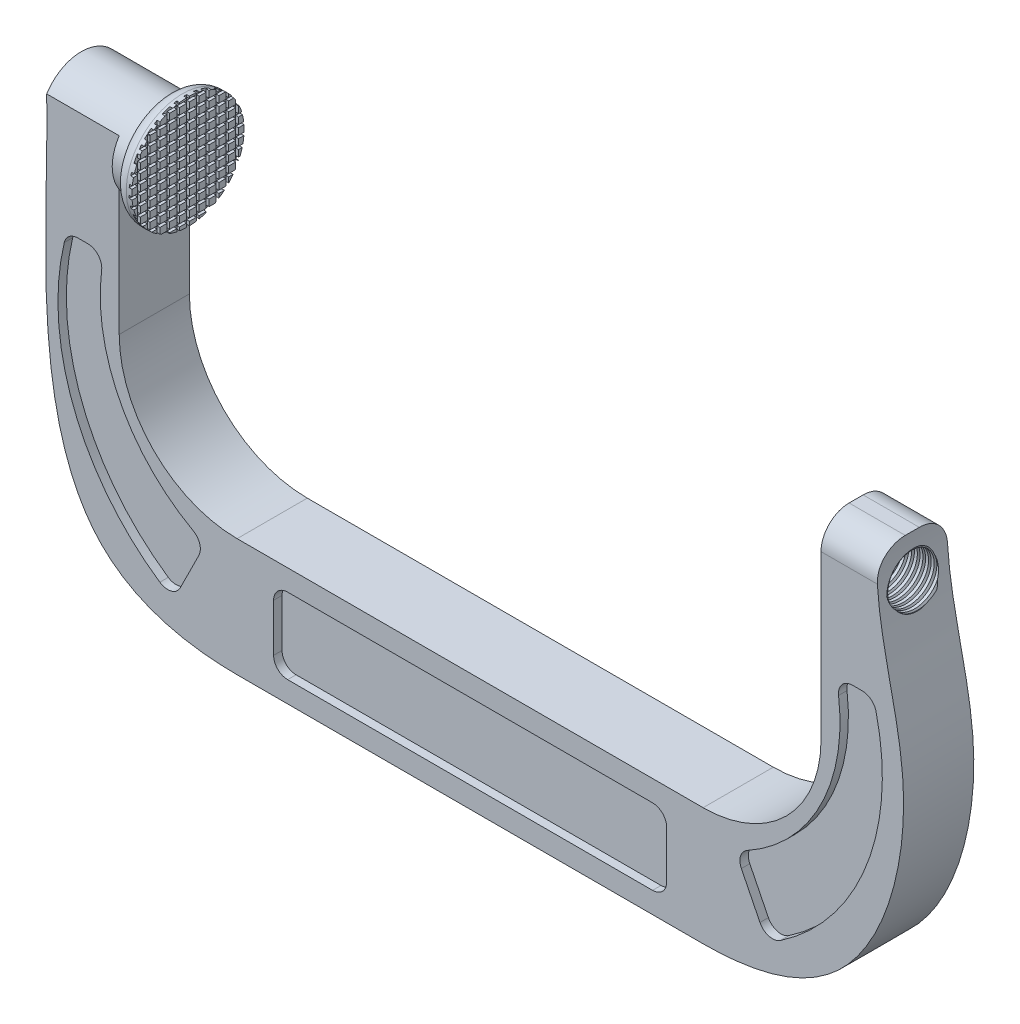
SolidWorks part; units mm, degrees
ref_plane "Front Plane" through (0, 0, 0) normal (0, 0, 1) x (1, 0, 0)
ref_plane "Top Plane" through (0, 0, 0) normal (0, 1, 0) x (1, 0, 0)
ref_plane "Right Plane" through (0, 0, 0) normal (1, 0, 0) x (0, 0, -1)
sketch "Sketch1" plane through (0, 0, 0) normal (0, 0, 1) x (1, 0, 0)
  line L0 (-263.6404, 0) -> (263.6404, 0) construction
  line L1 (125, 0) -> (125, -68)
  line L2 (83, -110) -> (-83, -110)
  line L3 (-125, -68) -> (-125, 0)
  line L4 (83, -152) -> (-83, -152)
  line L5 (0, 0) -> (0, -239.3038) construction
  line L6 (-151, 0) -> (-151, -68)
  line L7 (-151, 0) -> (-125, 0)
  line L8 (125, 0) -> (145, 0)
  arc A0 (125, -68) -> (83, -110) centre (83, -68) cw
  arc A1 (-83, -110) -> (-125, -68) centre (-83, -68) cw
  arc A4 (-83, -152) -> (-167, -68) centre (-83, -68) cw construction
  arc A5 (167, -68) -> (83, -152) centre (83, -68) cw construction
  spline S0 degree 3 poles (145, 0) (143.8087, -23.9152) (162.6478, -65.6261) (142.699, -139.1924) (104.3754, -151.9598) (83, -152) knots 0 0 0 0 0.358889 0.726266 1 1 1 1
  spline S1 degree 3 poles (-151, 0) (-150.1809, -23.6191) (-153.4891, -65.5445) (-144.2173, -139.5495) (-104.5553, -151.9594) (-83, -152) knots 0 0 0 0 0.358512 0.723962 1 1 1 1
  point P4 (0, 0)
  dimension "D4" = 42
  dimension "D1" = 250
  dimension "D2" = 125
  dimension "D3" = 110
  dimension "D5" = 42
  dimension "D6" = 20
  dimension "D7" = 26
  dimension "D8" = 132.4464
  dimension "D9" = 149.4354
  dimension "D10" = 154.2894
  dimension "D11" = 132.4464
  dimension "D12" = 37.3596
  dimension "D13" = 134.7867
extrude "Boss-Extrude1" add sketch "Sketch1" along normal mid plane 25 contours L7 S1 L6 L4 S0 L8 L1 A0 L2 A1 L3
sketch "Sketch2" plane through (-125, 0, 0) normal (1, 0, 0) x (0, 0, -1)
  line L0 (-12.5, 0) -> (12.5, 0) construction
  line L1 (-12.5, -68) -> (-12.5, 0) construction
  circle A0 centre (0, -15) radius 15
  dimension "D1" = 12.5
  dimension "D2" = 30
extrude "Boss-Extrude2" add sketch "Sketch2" along normal blind 5
sketch "Sketch3" plane through (-125, 0, 0) normal (1, 0, 0) x (0, 0, -1)
  line L2 (0, 0) -> (-12.5, 0)
  line L3 (-12.5, 0) -> (-12.5, -6.7084)
  line L4 (0, 0) -> (-12.5, 0)
  line L5 (-12.5, 0) -> (-12.5, -6.7084)
  line L6 (12.5, -6.7084) -> (12.5, 0)
  line L7 (12.5, 0) -> (0, 0)
  line L8 (12.5, -6.7084) -> (12.5, 0)
  line L9 (12.5, 0) -> (0, 0)
  arc A1 (0, 0) -> (-12.5, -6.7084) centre (0, -15) ccw
  arc A2 (0, 0) -> (-12.5, -6.7084) centre (0, -15) ccw
  arc A3 (12.5, -6.7084) -> (0, 0) centre (0, -15) ccw
  arc A4 (12.5, -6.7084) -> (0, 0) centre (0, -15) ccw
  dimension "D1" = 0
  dimension "D2" = 0
extrude "Cut-Extrude1" cut sketch "Sketch3" against normal through all contours A4 L8 L9
sketch "Sketch4" plane through (-120, 0, 0) normal (1, 0, 0) x (0, 0, -1)
  circle A0 centre (0, -15) radius 20
  circle A2 centre (0, -15) radius 15 construction
  dimension "D1" = 40
extrude "Boss-Extrude3" add sketch "Sketch4" along normal blind 7
fillet "Fillet1" radius 5 1 edges at (-120, -15, -20)
sketch "Sketch5" plane through (125, 0, 0) normal (-1, 0, 0) x (0, 0, 1)
  circle A1 centre (0, -15) radius 8.78
  dimension "D1" = 17.56
extrude "Cut-Extrude2" cut sketch "Sketch5" against normal through all
sketch "Sketch6" plane through (125, 0, 0) normal (-1, 0, 0) x (0, 0, 1)
  circle A0 centre (0, -15) radius 8.78 construction
  circle A1 centre (0, -15) radius 8.78
curve "Helix/Spiral1" pitch 2 height 30 radius 8.78 centre (125, -15, 0) axis (1, 0, 0) start towards (0, 1, 0)
sketch "Sketch7" plane through (0, 0, 0) normal (0, 0, 1) x (1, 0, 0)
  line L7 (125.7044, -6.6267) -> (125, -5.4067)
  line L8 (125, -5.4067) -> (124.2956, -6.6267)
  line L9 (124.2956, -6.6267) -> (125.7044, -6.6267)
  circle A0 centre (125, -6.22) radius 0.4067 construction
  dimension "D1" = 1.22
sweep "Cut-Sweep1" cut profiles "Sketch7" path "Helix/Spiral1" align with end faces yes
fillet "Fillet2" radius 10 2 edges at (135, 0, -12.5) (135, 0, 12.5)
sketch "Sketch8" plane through (0, 0, 12.5) normal (0, 0, 1) x (1, 0, 0)
  line L0 (0, 0) -> (0, -273.0897) construction
  line L1 (83, -110) -> (-83, -110) construction
  line L2 (-70, -117.5) -> (70, -117.5)
  line L3 (-70, -117.5) -> (-70, -144.5)
  line L4 (-70, -144.5) -> (70, -144.5)
  line L5 (70, -117.5) -> (70, -144.5)
  line L6 (-70, -117.5) -> (70, -144.5) construction
  line L7 (-70, -144.5) -> (70, -117.5) construction
  line L8 (130.2763, -45.612) -> (143.5579, -45.612)
  line L9 (94.4159, -117.5) -> (105.7053, -140.2435)
  line L10 (-94.4159, -117.5) -> (-105.7053, -140.2435)
  line L11 (-130.2763, -45.612) -> (-143.5579, -45.612)
  arc A0 (130.2763, -45.612) -> (94.4159, -117.5) centre (67.7918, -59.3307) cw
  arc A1 (105.7053, -140.2435) -> (143.5579, -45.612) centre (63.9991, -68.6747) ccw
  arc A4 (-105.7053, -140.2435) -> (-143.5579, -45.612) centre (-63.9991, -68.6747) cw
  arc A5 (-130.2763, -45.612) -> (-94.4159, -117.5) centre (-67.7918, -59.3307) ccw
  point P3 (0, -131)
  dimension "D1" = 27
  dimension "D2" = 140
  dimension "D3" = 21
extrude "Cut-Extrude3" cut sketch "Sketch8" against normal blind 3
fillet "Fillet3" radius 5 12 edges at (-143.5579, -45.612, 11) (-130.2763, -45.612, 11) (-94.4159, -117.5, 11) (-105.7053, -140.2435, 11) (105.7053, -140.2435, 11) (94.4159, -117.5, 11) (130.2763, -45.612, 11) (143.5579, -45.612, 11) (70, -144.5, 11) (70, -117.5, 11) (-70, -144.5, 11) (-70, -117.5, 11)
mirror "Mirror2" about plane through (0, 0, 0) normal (0, 0, 1) of "Fillet3", "Cut-Extrude3"
sketch "Sketch9" plane through (-113, 0, 0) normal (1, 0, 0) x (0, 0, -1)
  line L0 (0, 0) -> (0, 50000) construction
  line L1 (0, 0) -> (50000, 0) construction
  line L2 (-22.5, -0.1) -> (-22.5, 0.9)
  line L3 (-22.5, 3.25) -> (22.5, 3.25)
  line L4 (-22.5, 3.25) -> (-22.5, 4.25)
  line L5 (-22.5, 4.25) -> (22.5, 4.25)
  line L6 (22.5, 3.25) -> (22.5, 4.25)
  line L7 (-22.5, 3.25) -> (22.5, 4.25) construction
  line L8 (-22.5, 4.25) -> (22.5, 3.25) construction
  line L9 (-22.5, -0.1) -> (22.5, -0.1)
  line L10 (22.5, -0.1) -> (22.5, 0.9)
  line L11 (-22.5, 0.9) -> (22.5, 0.9)
  line L12 (-22.5, -3.45) -> (-22.5, -2.45)
  line L13 (-22.5, -3.45) -> (22.5, -3.45)
  line L14 (22.5, -3.45) -> (22.5, -2.45)
  line L15 (-22.5, -2.45) -> (22.5, -2.45)
  line L16 (-22.5, -6.8) -> (-22.5, -5.8)
  line L17 (-22.5, -6.8) -> (22.5, -6.8)
  line L18 (22.5, -6.8) -> (22.5, -5.8)
  line L19 (-22.5, -5.8) -> (22.5, -5.8)
  line L20 (-22.5, -10.15) -> (-22.5, -9.15)
  line L21 (-22.5, -10.15) -> (22.5, -10.15)
  line L22 (22.5, -10.15) -> (22.5, -9.15)
  line L23 (-22.5, -9.15) -> (22.5, -9.15)
  line L24 (-22.5, -13.5) -> (-22.5, -12.5)
  line L25 (-22.5, -13.5) -> (22.5, -13.5)
  line L26 (22.5, -13.5) -> (22.5, -12.5)
  line L27 (-22.5, -12.5) -> (22.5, -12.5)
  line L28 (-22.5, -16.85) -> (-22.5, -15.85)
  line L29 (-22.5, -16.85) -> (22.5, -16.85)
  line L30 (22.5, -16.85) -> (22.5, -15.85)
  line L31 (-22.5, -15.85) -> (22.5, -15.85)
  line L32 (-22.5, -20.2) -> (-22.5, -19.2)
  line L33 (-22.5, -20.2) -> (22.5, -20.2)
  line L34 (22.5, -20.2) -> (22.5, -19.2)
  line L35 (-22.5, -19.2) -> (22.5, -19.2)
  line L36 (-22.5, -23.55) -> (-22.5, -22.55)
  line L37 (-22.5, -23.55) -> (22.5, -23.55)
  line L38 (22.5, -23.55) -> (22.5, -22.55)
  line L39 (-22.5, -22.55) -> (22.5, -22.55)
  line L40 (-22.5, -26.9) -> (-22.5, -25.9)
  line L41 (-22.5, -26.9) -> (22.5, -26.9)
  line L42 (22.5, -26.9) -> (22.5, -25.9)
  line L43 (-22.5, -25.9) -> (22.5, -25.9)
  line L44 (-22.5, -30.25) -> (-22.5, -29.25)
  line L45 (-22.5, -30.25) -> (22.5, -30.25)
  line L46 (22.5, -30.25) -> (22.5, -29.25)
  line L47 (-22.5, -29.25) -> (22.5, -29.25)
  line L48 (-22.5, -33.6) -> (-22.5, -32.6)
  line L49 (-22.5, -33.6) -> (22.5, -33.6)
  line L50 (22.5, -33.6) -> (22.5, -32.6)
  line L51 (-22.5, -32.6) -> (22.5, -32.6)
  point P5 (0, 3.75)
  dimension "D1" = 45
  dimension "D2" = 1
  dimension "D4" = 2.35
  dimension "D5" = 3.25
  dimension "D3" = 12
extrude "Cut-Extrude4" cut sketch "Sketch9" against normal blind 1
sketch "Sketch10" plane through (-113, 0, 0) normal (1, 0, 0) x (0, 0, -1)
  line L0 (0, -0.1) -> (0, 49999.9) construction
  line L1 (-13.3413, -0.1) -> (13.3413, -0.1) construction
  line L2 (3, -40) -> (3, 40)
  line L3 (-0.5, -40) -> (0.5, -40)
  line L4 (-0.5, -40) -> (-0.5, 40)
  line L5 (-0.5, 40) -> (0.5, 40)
  line L6 (0.5, -40) -> (0.5, 40)
  line L7 (-0.5, -40) -> (0.5, 40) construction
  line L8 (-0.5, 40) -> (0.5, -40) construction
  line L9 (3, -40) -> (4, -40)
  line L10 (4, -40) -> (4, 40)
  line L11 (3, 40) -> (4, 40)
  line L12 (6.5, -40) -> (6.5, 40)
  line L13 (6.5, -40) -> (7.5, -40)
  line L14 (7.5, -40) -> (7.5, 40)
  line L15 (6.5, 40) -> (7.5, 40)
  line L16 (10, -40) -> (10, 40)
  line L17 (10, -40) -> (11, -40)
  line L18 (11, -40) -> (11, 40)
  line L19 (10, 40) -> (11, 40)
  line L20 (13.5, -40) -> (13.5, 40)
  line L21 (13.5, -40) -> (14.5, -40)
  line L22 (14.5, -40) -> (14.5, 40)
  line L23 (13.5, 40) -> (14.5, 40)
  line L24 (17, -40) -> (17, 40)
  line L25 (17, -40) -> (18, -40)
  line L26 (18, -40) -> (18, 40)
  line L27 (17, 40) -> (18, 40)
  line L28 (-17, -40) -> (-18, -40)
  line L29 (-18, -40) -> (-18, 40)
  line L30 (-17, 40) -> (-18, 40)
  line L31 (-17, -40) -> (-17, 40)
  line L32 (-13.5, -40) -> (-14.5, -40)
  line L33 (-14.5, -40) -> (-14.5, 40)
  line L34 (-13.5, 40) -> (-14.5, 40)
  line L35 (-13.5, -40) -> (-13.5, 40)
  line L36 (-10, -40) -> (-11, -40)
  line L37 (-11, -40) -> (-11, 40)
  line L38 (-10, 40) -> (-11, 40)
  line L39 (-10, -40) -> (-10, 40)
  line L40 (-6.5, -40) -> (-7.5, -40)
  line L41 (-7.5, -40) -> (-7.5, 40)
  line L42 (-6.5, 40) -> (-7.5, 40)
  line L43 (-6.5, -40) -> (-6.5, 40)
  line L44 (-3, -40) -> (-4, -40)
  line L45 (-4, -40) -> (-4, 40)
  line L46 (-3, 40) -> (-4, 40)
  line L47 (-3, -40) -> (-3, 40)
  point P4 (0, -0.1)
  point P5 (0, 0)
  dimension "D1" = 1
  dimension "D2" = 80
  dimension "D4" = 2.5
  dimension "D3" = 6
extrude "Cut-Extrude5" cut sketch "Sketch10" against normal blind 1
